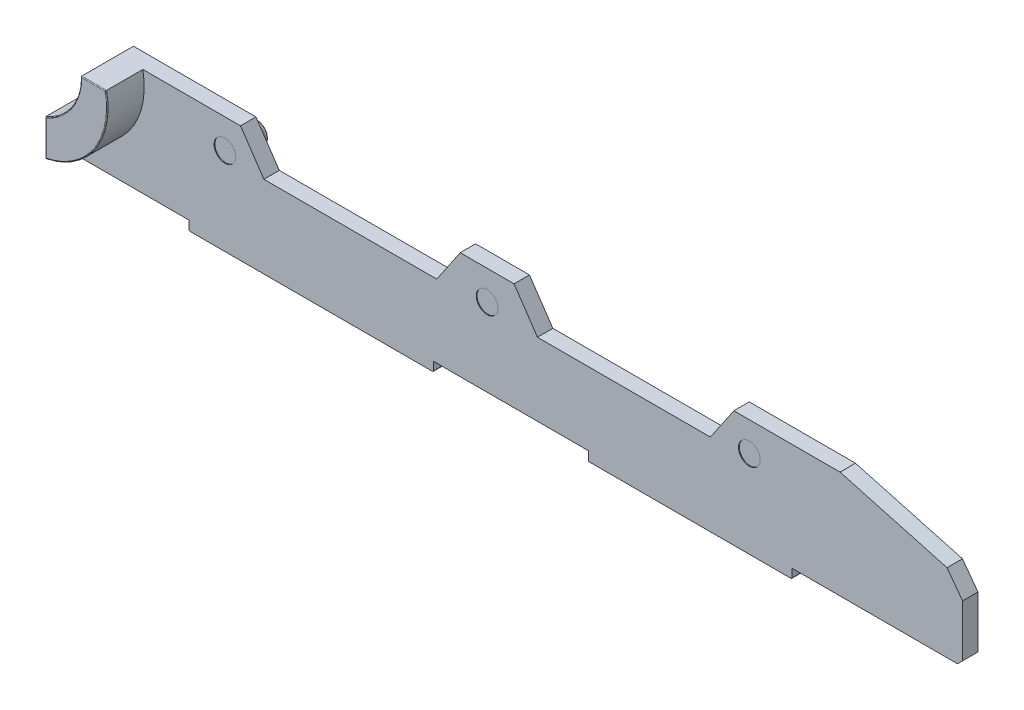
SolidWorks part; units mm, degrees
ref_plane "Front Plane" through (0, 0, 0) normal (0, 0, 1) x (1, 0, 0)
ref_plane "Top Plane" through (0, 0, 0) normal (0, 1, 0) x (1, 0, 0)
ref_plane "Right Plane" through (0, 0, 0) normal (1, 0, 0) x (0, 0, -1)
sketch "Sketch1" plane through (0, 0, 0) normal (0, 0, 1) x (1, 0, 0)
  line L0 (0, 0) -> (113.56, 0)
  line L1 (84.5347, 13.93) -> (81.487, 9.45)
  line L2 (113.56, 0) -> (114.2247, 0.6647)
  line L3 (114.2247, 0.6647) -> (114.2247, 7.4047)
  line L4 (112.2063, 10.1283) -> (114.2247, 7.4047)
  line L5 (98.3247, 13.93) -> (112.2063, 10.1283)
  line L7 (114.2195, 13.9272) -> (98.3195, 13.93) construction
  line L8 (98.3247, 13.93) -> (84.5347, 13.93)
  line L9 (81.487, 9.45) -> (59.047, 9.45)
  line L10 (84.5347, 9.45) -> (148.7022, 9.45) construction
  line L11 (59.047, 9.45) -> (56.0076, 13.9376)
  line L12 (56.0076, 13.9376) -> (49.0176, 13.9388)
  line L13 (49.0176, 13.9388) -> (45.98, 9.45)
  line L14 (45.98, 9.45) -> (23.54, 9.45)
  line L15 (23.54, 9.45) -> (20.51, 13.9439)
  line L16 (20.51, 13.9439) -> (4.61, 13.9468)
  line L17 (0, 7.11) -> (0, 0)
  arc A0 (4.61, 13.9468) -> (0, 7.11) centre (-2.7665, 13.9481) cw
  dimension "D1" = 113.56
  dimension "D2" = 5.4184
  dimension "D3" = 0.94
  dimension "D4" = 6.74
  dimension "D5" = 13.79
  dimension "D7" = 22.44
  dimension "D8" = 5.42
  dimension "D9" = 6.99
  dimension "D10" = 5.42
  dimension "D11" = 22.44
  dimension "D12" = 5.42
  dimension "D13" = 15.9
  dimension "D14" = 7.11
extrude "Boss-Extrude1" add sketch "Sketch1" along normal blind 2
sketch "Sketch4" plane through (0, 0, 2) normal (0, 0, 1) x (1, 0, 0)
  line L0 (20.51, 13.9439) -> (4.61, 13.9468) construction
  line L1 (56.0076, 13.9376) -> (49.0176, 13.9388) construction
  line L2 (98.3247, 13.93) -> (84.5347, 13.93) construction
  line L3 (23.54, 9.45) -> (20.51, 13.9439) construction
  line L4 (84.5347, 13.93) -> (81.487, 9.45) construction
  circle A0 centre (52.5125, 10.1282) radius 1.41
  circle A1 centre (18.4835, 10.1343) radius 1.41
  circle A2 centre (86.5508, 10.12) radius 1.41
  circle A3 centre (18.4835, 10.1343) radius 1.41
  dimension "D1" = 2.82
  dimension "D2" = 3.81
  dimension "D3" = 2.82
  dimension "D4" = 2.82
  dimension "D5" = 3.81
  dimension "D6" = 3.81
  dimension "D7" = 3.81
  dimension "D8" = 3.81
  dimension "D9" = 3.81
sketch "Sketch6" plane through (0, 0, 0) normal (0, -1, 0) x (1, 0, 0)
  line L0 (0, 2) -> (13.83, 2) construction
  line L1 (0, 2) -> (113.56, 2) construction
  line L2 (13.83, 2) -> (45.53, 2)
  line L3 (13.83, 2) -> (13.83, 0.8)
  line L4 (13.83, 0.8) -> (45.53, 0.8)
  line L5 (45.53, 0.8) -> (45.53, 2)
  dimension "D1" = 13.83
  dimension "D2" = 31.7
  dimension "D3" = 1.2
extrude "Boss-Extrude2" add sketch "Sketch6" along normal blind 1.2
sketch "Sketch7" plane through (0, 0, 0) normal (0, -1, 0) x (-1, 0, 0)
  line L1 (-45.53, -2) -> (-113.56, -2) construction
  line L2 (-65.68, -2) -> (-92.06, -2)
  line L3 (-65.68, -2) -> (-65.68, -0.8)
  line L4 (-65.68, -0.8) -> (-92.06, -0.8)
  line L5 (-92.06, -0.8) -> (-92.06, -2)
  dimension "D2" = 26.38
  dimension "D3" = 1.2
extrude "Boss-Extrude3" add sketch "Sketch7" along normal blind 1.2
extrude "Cut-Extrude6" cut sketch "Sketch4" against normal blind 0.1 contours A2 | A0 | A1
sketch "Sketch18" plane through (0, 0, 2) normal (0, 0, 1) x (1, 0, 0)
  line L0 (4.61, 13.9468) -> (7.83, 13.9462)
  line L1 (20.51, 13.9439) -> (4.61, 13.9468) construction
  line L2 (0, 7.11) -> (0, 2.37)
  line L3 (0, 7.11) -> (0, 0) construction
  arc A0 (4.61, 13.9468) -> (0, 7.11) centre (-2.7665, 13.9481) cw
  arc A1 (7.83, 13.9462) -> (0, 2.37) centre (-1.8731, 12.0731) cw
  dimension "D1" = 3.22
  dimension "D2" = 4.74
extrude "Boss-Extrude11" add sketch "Sketch18" along normal blind 4.8
shell "Shell10" thickness 1.2 removed face at (61.1449, 9.1269, 0)
fillet "Fillet2" radius 2 1 edges at (5.4566, 7.4194, 0.8)
sketch "Sketch19" plane through (0, 0, 0.8) normal (0, 0, -1) x (-1, 0, 0)
  line L0 (-112.1047, 8.25) -> (-113.0247, 7.0085)
  line L1 (-113.0247, 7.0085) -> (-111.4892, 9.0805) construction
  line L2 (-112.1047, 8.25) -> (-8.1016, 8.25)
  line L3 (-113.0247, 7.0085) -> (-7.5322, 7.0085)
  arc A0 (-8.7879, 12.746) -> (-1.2, 1.8424) centre (1.8731, 12.0731) ccw construction
  arc A1 (-7.5322, 7.0085) -> (-8.1016, 8.25) centre (1.8731, 12.0731) cw
extrude "Boss-Extrude12" add sketch "Sketch19" along normal blind 0.5
sketch "Sketch27" plane through (0, 0, 0.7) normal (0, 0, -1) x (-1, 0, 0)
  circle A1 centre (-52.5125, 10.1282) radius 1.5
  dimension "D1" = 3
extrude "Boss-Extrude13" add sketch "Sketch27" along normal blind 3 contours A1
fillet "Fillet3" radius 0.5 1 edges at (51.0125, 10.1282, -2.3)
sketch "Sketch32" plane through (0, 0, 0.7) normal (0, 0, -1) x (-1, 0, 0)
  circle A0 centre (-86.5508, 10.12) radius 1.5
  dimension "D1" = 3
extrude "Boss-Extrude14" add sketch "Sketch32" along normal blind 3
fillet "Fillet4" radius 0.5 1 edges at (85.0508, 10.12, -2.3)
sketch "Sketch33" plane through (0, 0, 0.7) normal (0, 0, -1) x (-1, 0, 0)
  circle A0 centre (-18.4835, 10.1343) radius 1.5
  dimension "D1" = 3
extrude "Boss-Extrude15" add sketch "Sketch33" along normal blind 3
fillet "Fillet5" radius 0.5 1 edges at (16.9835, 10.1343, -2.3)
sketch "Sketch34" plane through (0, 0, -2.3) normal (0, 0, -1) x (-1, 0, 0)
  circle A0 centre (-52.5125, 10.1282) radius 0.5
extrude "Cut-Extrude7" cut sketch "Sketch34" against normal blind 3
sketch "Sketch35" plane through (0, 0, -2.3) normal (0, 0, -1) x (-1, 0, 0)
  circle A0 centre (-18.4835, 10.1343) radius 0.5
extrude "Cut-Extrude8" cut sketch "Sketch35" against normal blind 3
sketch "Sketch36" plane through (0, 0, -2.3) normal (0, 0, -1) x (-1, 0, 0)
  circle A0 centre (-86.5508, 10.12) radius 0.5
extrude "Cut-Extrude9" cut sketch "Sketch36" against normal blind 3
fillet "Fillet7" radius 0.1 4 edges at (6.22, 13.9465, 6.8) (6.3125, 6.5365, 6.8) (0, 4.74, 6.8) (3.3495, 9.8241, 6.8)
fillet "Fillet8" radius 0.1 1 edges at (13.83, -1.2, 1.4)
fillet "Fillet9" radius 0.1 1 edges at (92.06, -1.2, 1.4)
fillet "Fillet10" radius 0.1 1 edges at (65.68, -1.2, 1.4)
fillet "Fillet11" radius 0.1 1 edges at (45.53, -1.2, 1.4)
